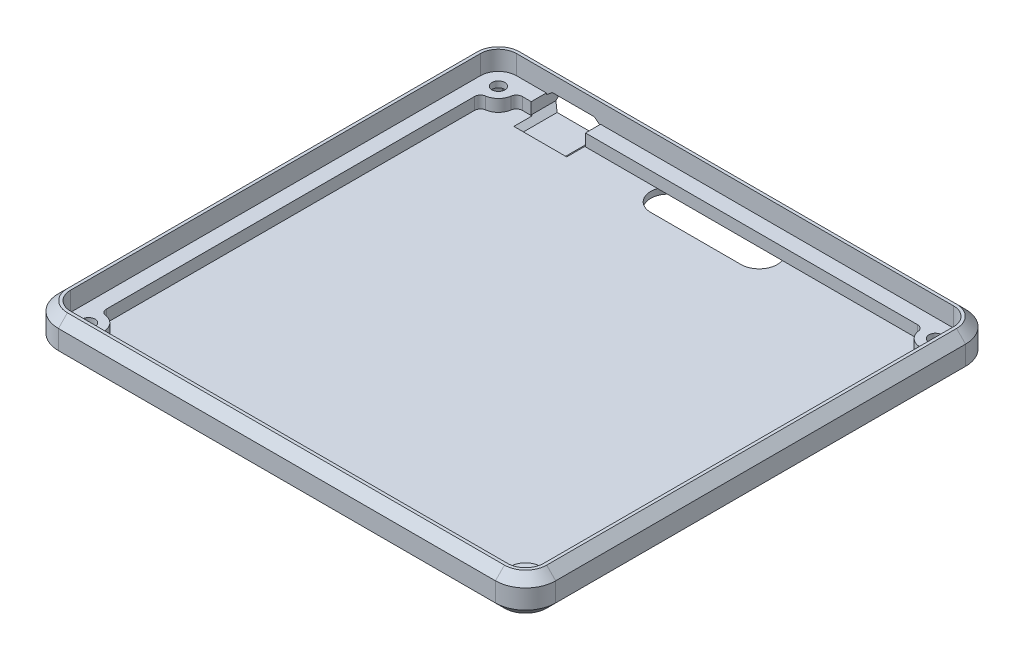
SolidWorks part; units mm, degrees
material "ABS"
ref_plane "Front Plane" through (0, 0, 0) normal (0, 0, 1) x (1, 0, 0)
ref_plane "Top Plane" through (0, 0, 0) normal (0, 1, 0) x (1, 0, 0)
ref_plane "Right Plane" through (0, 0, 0) normal (1, 0, 0) x (0, 0, -1)
sketch "Sketch2" plane through (0, 0, 0) normal (0, 1, 0) x (1, 0, 0)
  line L1 (-72.5, 74) -> (72.5, 74)
  line L2 (-78.5, 68) -> (-78.5, -68)
  line L3 (-72.5, -74) -> (72.5, -74)
  line L4 (78.5, 68) -> (78.5, -68)
  line L5 (-78.5, 74) -> (78.5, -74) construction
  line L6 (-78.5, -74) -> (78.5, 74) construction
  arc A0 (-78.5, -68) -> (-72.5, -74) centre (-72.5, -68) ccw
  arc A1 (-72.5, 74) -> (-78.5, 68) centre (-72.5, 68) ccw
  arc A2 (72.5, 74) -> (78.5, 68) centre (72.5, 68) cw
  arc A3 (72.5, -74) -> (78.5, -68) centre (72.5, -68) ccw
  point P0 (0, 0)
  dimension "D3" = 6
  dimension "D1" = 157
  dimension "D2" = 148
extrude "Boss-Extrude2" add sketch "Sketch2" along normal blind 2
sketch "Sketch3" plane through (0, 2, 0) normal (0, 1, 0) x (1, 0, 0)
  line L0 (-72.5, -74) -> (72.5, -74) construction
  line L1 (78.5, -68) -> (78.5, 68) construction
  line L2 (72.5, 74) -> (-72.5, 74) construction
  line L3 (-78.5, 68) -> (-78.5, -68) construction
  line L4 (-72.5, -74) -> (72.5, -74)
  line L5 (78.5, -68) -> (78.5, 68)
  line L6 (72.5, 74) -> (-72.5, 74)
  line L7 (-78.5, 68) -> (-78.5, -68)
  line L8 (0, -80.5945) -> (0, 82.9206) construction
  line L9 (9.041, 0) -> (-113.0904, 0) construction
  line L10 (-82.5, 68) -> (-82.5, -68)
  line L11 (-72.5, -78) -> (72.5, -78)
  line L12 (82.5, -68) -> (82.5, 68)
  line L13 (72.5, 78) -> (-72.5, 78)
  line L14 (-73.5, 63) -> (-73.5, -63)
  line L15 (-67.5, -69) -> (67.5, -69)
  line L16 (73.5, -63) -> (73.5, 63)
  line L17 (67.5, 69) -> (-67.5, 69)
  line L18 (-73.5, 63) -> (-72.5, 63)
  line L19 (-67.5, 69) -> (-67.5, 68)
  line L20 (-73.5, 68) -> (-73.5, -68) construction
  line L21 (72.5, 69) -> (-72.5, 69) construction
  line L22 (67.5, 69) -> (67.5, 68)
  line L23 (73.5, 63) -> (72.5, 63)
  line L24 (67.5, -69) -> (67.5, -68)
  line L25 (73.5, -63) -> (72.5, -63)
  line L26 (-67.5, -69) -> (-67.5, -68)
  line L27 (-73.5, -63) -> (-72.5, -63)
  line L28 (-72.5, -69) -> (72.5, -69) construction
  line L29 (73.5, -68) -> (73.5, 68) construction
  arc A0 (-78.5, -68) -> (-72.5, -74) centre (-72.5, -68) ccw construction
  arc A1 (72.5, -74) -> (78.5, -68) centre (72.5, -68) ccw construction
  arc A2 (78.5, 68) -> (72.5, 74) centre (72.5, 68) ccw construction
  arc A3 (-72.5, 74) -> (-78.5, 68) centre (-72.5, 68) ccw construction
  arc A4 (-78.5, -68) -> (-72.5, -74) centre (-72.5, -68) ccw
  arc A5 (72.5, -74) -> (78.5, -68) centre (72.5, -68) ccw
  arc A6 (78.5, 68) -> (72.5, 74) centre (72.5, 68) ccw
  arc A7 (-72.5, 74) -> (-78.5, 68) centre (-72.5, 68) ccw
  circle A9 centre (-72.5, -68) radius 2.15
  circle A10 centre (72.5, -68) radius 2.15
  circle A11 centre (72.5, 68) radius 2.15
  circle A12 centre (-72.5, 68) radius 2.15
  arc A13 (-82.5, -68) -> (-72.5, -78) centre (-72.5, -68) ccw
  arc A14 (72.5, -78) -> (82.5, -68) centre (72.5, -68) ccw
  arc A15 (82.5, 68) -> (72.5, 78) centre (72.5, 68) ccw
  arc A16 (-72.5, 78) -> (-82.5, 68) centre (-72.5, 68) ccw
  arc A21 (-72.5, 63) -> (-67.5, 68) centre (-72.5, 68) ccw
  arc A22 (72.5, 63) -> (67.5, 68) centre (72.5, 68) cw
  arc A23 (-72.5, 69) -> (-73.5, 68) centre (-72.5, 68) ccw construction
  arc A24 (72.5, -63) -> (67.5, -68) centre (72.5, -68) ccw
  arc A25 (-72.5, -63) -> (-67.5, -68) centre (-72.5, -68) cw
  arc A26 (-73.5, -68) -> (-72.5, -69) centre (-72.5, -68) ccw construction
  arc A27 (72.5, -69) -> (73.5, -68) centre (72.5, -68) ccw construction
  arc A28 (73.5, 68) -> (72.5, 69) centre (72.5, 68) ccw construction
  arc M10 (-78.5, -68) -> (-72.5, -74) centre (-72.5, -68) ccw
  line M11 (-72.5, -74) -> (72.5, -74)
  arc M12 (72.5, -74) -> (78.5, -68) centre (72.5, -68) ccw
  line M13 (78.5, -68) -> (78.5, 68)
  arc M14 (78.5, 68) -> (72.5, 74) centre (72.5, 68) ccw
  line M15 (72.5, 74) -> (-72.5, 74)
  arc M16 (-72.5, 74) -> (-78.5, 68) centre (-72.5, 68) ccw
  line M17 (-78.5, 68) -> (-78.5, -68)
  dimension "D1" = 68
  dimension "D2" = 4.3
  dimension "D3" = 72.5
  dimension "D4" = 4
  dimension "D6" = 1
  dimension "D7" = 5
  dimension "D8" = 1
  dimension "D9" = 5
  dimension "D5" = 5
extrude "Boss-Extrude3" add sketch "Sketch3" along normal blind 4 and the other way blind 2 contours L13 A16 L10 A13 L11 A14 L12 A15 M10 M17 M16 M15 M14 M13 M12 M11 | L17 L16 L15 L14 M17 M10 M11 M12 M13 M14 M15 M16 region at (-75.217, 2, 70.717) region at (-77.9654, 2, -73.4654)
sketch "Sketch8" plane through (0, 6, 0) normal (0, 1, 0) x (1, 0, 0)
  line L0 (-72.5, -78) -> (72.5, -78) construction
  line L1 (82.5, -68) -> (82.5, 68) construction
  line L2 (72.5, 78) -> (-72.5, 78) construction
  line L3 (-82.5, 68) -> (-82.5, -68) construction
  line L4 (78.5, -68) -> (78.5, 68)
  line L5 (72.5, 74) -> (-72.5, 74)
  line L6 (-78.5, 68) -> (-78.5, -68)
  line L7 (-72.5, -74) -> (72.5, -74)
  line L8 (78.5, -68) -> (78.5, 68)
  line L9 (72.5, 74) -> (-72.5, 74)
  line L10 (-78.5, 68) -> (-78.5, -68)
  line L11 (-72.5, -74) -> (72.5, -74)
  line L12 (-72.5, -78) -> (72.5, -78)
  line L13 (82.5, -68) -> (82.5, 68)
  line L14 (72.5, 78) -> (-72.5, 78)
  line L15 (-82.5, 68) -> (-82.5, -68)
  line L16 (-77.5, 68) -> (-77.5, -68)
  line L17 (-72.5, -73) -> (72.5, -73)
  line L18 (77.5, -68) -> (77.5, 68)
  line L19 (72.5, 73) -> (-72.5, 73)
  arc A0 (-82.5, -68) -> (-72.5, -78) centre (-72.5, -68) ccw construction
  arc A1 (72.5, -78) -> (82.5, -68) centre (72.5, -68) ccw construction
  arc A2 (82.5, 68) -> (72.5, 78) centre (72.5, 68) ccw construction
  arc A3 (-72.5, 78) -> (-82.5, 68) centre (-72.5, 68) ccw construction
  arc A4 (78.5, 68) -> (72.5, 74) centre (72.5, 68) ccw
  arc A5 (-72.5, 74) -> (-78.5, 68) centre (-72.5, 68) ccw
  arc A6 (-78.5, -68) -> (-72.5, -74) centre (-72.5, -68) ccw
  arc A7 (72.5, -74) -> (78.5, -68) centre (72.5, -68) ccw
  arc A8 (78.5, 68) -> (72.5, 74) centre (72.5, 68) ccw
  arc A9 (-72.5, 74) -> (-78.5, 68) centre (-72.5, 68) ccw
  arc A10 (-78.5, -68) -> (-72.5, -74) centre (-72.5, -68) ccw
  arc A11 (72.5, -74) -> (78.5, -68) centre (72.5, -68) ccw
  arc A12 (-82.5, -68) -> (-72.5, -78) centre (-72.5, -68) ccw
  arc A13 (72.5, -78) -> (82.5, -68) centre (72.5, -68) ccw
  arc A14 (82.5, 68) -> (72.5, 78) centre (72.5, 68) ccw
  arc A15 (-72.5, 78) -> (-82.5, 68) centre (-72.5, 68) ccw
  arc A16 (-77.5, -68) -> (-72.5, -73) centre (-72.5, -68) ccw
  arc A17 (72.5, -73) -> (77.5, -68) centre (72.5, -68) ccw
  arc A18 (77.5, 68) -> (72.5, 73) centre (72.5, 68) ccw
  arc A19 (-72.5, 73) -> (-77.5, 68) centre (-72.5, 68) ccw
  line M17 (72.5, 78) -> (-72.5, 78)
  arc M18 (-72.5, 78) -> (-82.5, 68) centre (-72.5, 68) ccw
  line M19 (-82.5, 68) -> (-82.5, -68)
  arc M20 (-82.5, -68) -> (-72.5, -78) centre (-72.5, -68) ccw
  line M21 (-72.5, -78) -> (72.5, -78)
  arc M22 (72.5, -78) -> (82.5, -68) centre (72.5, -68) ccw
  line M23 (82.5, -68) -> (82.5, 68)
  arc M24 (82.5, 68) -> (72.5, 78) centre (72.5, 68) ccw
  dimension "D1" = 0
  dimension "D2" = 5
extrude "Boss-Extrude4" add sketch "Sketch8" along normal blind 6.38 contours A11 L11 A10 L10 A9 L9 A8 L8 M24 M17 M18 M19 M20 M21 M22 M23 region at (-77.9654, 6, 73.4654)
sketch "Sketch9" plane through (0, 0, -78) normal (0, 0, -1) x (-1, 0, 0)
  line L0 (82.5, 0) -> (82.5, 12.38) construction
  line L7 (60.62, 7.11) -> (46.62, 7.11)
  line L8 (46.62, 7.11) -> (44.62, 5.51)
  line L14 (62.62, 5.51) -> (60.62, 7.11)
  line L15 (54.9775, 3.85) -> (29.0731, 3.85) construction
  line L16 (44.62, 5.51) -> (44.62, 2.19)
  line L17 (62.62, 5.51) -> (62.62, 2.19)
  line L18 (53.62, 7.11) -> (53.62, 5.8424) construction
  line L19 (-72.5, 0) -> (72.5, 0) construction
  line L20 (62.62, 2.19) -> (60.62, 0.59)
  line L21 (60.62, 0.59) -> (46.62, 0.59)
  line L22 (46.62, 0.59) -> (44.62, 2.19)
  point P7 (62.62, 3.85)
  point P20 (44.62, 3.85)
  dimension "D2" = 3.85
  dimension "D1" = 28.88
  dimension "D5" = 3.26
  dimension "D6" = 1.66
  dimension "D7" = 18
  dimension "D8" = 14
extrude "Cut-Extrude1" cut sketch "Sketch9" against normal blind 15
fillet "Fillet1" radius 2 8 edges at (-67.5, 4, -69) (-73.5, 4, -63) (-73.5, 4, 63) (-67.5, 4, 69) (73.5, 4, 63) (67.5, 4, 69) (67.5, 4, -69) (73.5, 4, -63)
sketch "Sketch11" plane through (0, 2, 0) normal (0, 1, 0) x (1, 0, 0)
  circle A0 centre (-72.5, 68) radius 2.15
  circle A1 centre (72.5, 68) radius 2.15
  circle A2 centre (72.5, -68) radius 2.15
  circle A3 centre (-72.5, -68) radius 2.15
  dimension "D1" = 4.3
  dimension "D2" = 4.3
  dimension "D3" = 4.3
  dimension "D4" = 4.3
extrude "Cut-Extrude3" cut sketch "Sketch11" against normal through all both and the other way through all contours A3 | A2 | A1 | A0 region at (-72.5, 2, -68) region at (72.5, 2, -68) region at (72.5, 2, 68) region at (-72.5, 2, 68)
sketch "Sketch10" plane through (0, 0, 0) normal (0, -1, 0) x (1, 0, 0)
  line L0 (0, -78) -> (0, 105.632) construction
  line L1 (72.5, -78) -> (-72.5, -78) construction
  line L2 (-82.5, 0) -> (91.4068, 0) construction
  line L3 (-82.5, -68) -> (-82.5, 68) construction
  line L4 (70.4793, 64.5) -> (68.4585, 68)
  line L5 (-68.4585, 68) -> (-70.4793, 71.5)
  line L6 (-70.4793, 71.5) -> (-74.5207, 71.5)
  line L7 (-74.5207, 71.5) -> (-76.5415, 68)
  line L8 (-76.5415, 68) -> (-74.5207, 64.5)
  line L9 (-74.5207, 64.5) -> (-70.4793, 64.5)
  line L10 (-70.4793, 64.5) -> (-68.4585, 68)
  line L11 (74.5207, 64.5) -> (70.4793, 64.5)
  line L12 (76.5415, 68) -> (74.5207, 64.5)
  line L13 (74.5207, 71.5) -> (76.5415, 68)
  line L14 (70.4793, 71.5) -> (74.5207, 71.5)
  line L15 (68.4585, 68) -> (70.4793, 71.5)
  line L16 (74.5207, -64.5) -> (70.4793, -64.5)
  line L17 (76.5415, -68) -> (74.5207, -64.5)
  line L18 (74.5207, -71.5) -> (76.5415, -68)
  line L19 (70.4793, -71.5) -> (74.5207, -71.5)
  line L20 (68.4585, -68) -> (70.4793, -71.5)
  line L21 (70.4793, -64.5) -> (68.4585, -68)
  line L22 (-70.4793, -64.5) -> (-68.4585, -68)
  line L23 (-74.5207, -64.5) -> (-70.4793, -64.5)
  line L24 (-76.5415, -68) -> (-74.5207, -64.5)
  line L25 (-74.5207, -71.5) -> (-76.5415, -68)
  line L26 (-70.4793, -71.5) -> (-74.5207, -71.5)
  line L27 (-68.4585, -68) -> (-70.4793, -71.5)
  line L28 (-72.5, 68) -> (-62.8389, 68)
  circle A0 centre (-72.5, 68) radius 3.5 construction
  circle A1 centre (-72.5, 68) radius 2.15 construction
  dimension "D3" = 7
extrude "Cut-Extrude2" cut sketch "Sketch10" against normal blind 4 contours L9 L10 L5 L6 L7 L8 | L12 L11 L4 L15 L14 L13 | L22 L27 L26 L25 L24 L23 | L17 L16 L21 L20 L19 L18 region at (-69.5615, 0, 66.3035)
chamfer "Chamfer1" distance 3 angle 45 16 edges at (-79.5711, 12.38, 75.0711) (0, 12.38, 78) (79.5711, 12.38, 75.0711) (82.5, 12.38, 0) (79.5711, 12.38, -75.0711) (0, 12.38, -78) (-82.5, 12.38, 0) (-79.5711, 12.38, -75.0711) (-79.5711, 0, -75.0711) (-82.5, 0, 0) (-79.5711, 0, 75.0711) (0, 0, 78) (79.5711, 0, 75.0711) (82.5, 0, 0) (79.5711, 0, -75.0711) (0, 0, -78)
sketch "Sketch13" plane through (0, 6, 0) normal (0, 1, 0) x (1, 0, 0)
  line L0 (-53.62, 63) -> (-53.62, 80.4308) construction
  line L1 (-46.62, 63) -> (-60.62, 63) construction
  line L2 (-44.62, 69) -> (-62.62, 69)
  line L3 (65.5718, 69) -> (-45.2325, 69) construction
  line L4 (-62.0075, 69) -> (-65.5718, 69) construction
  line L5 (-62.62, 69) -> (-62.62, 74)
  line L6 (-62.0075, 74) -> (-72.5, 74) construction
  line L7 (-62.62, 74) -> (-44.62, 74)
  line L8 (72.5, 74) -> (-72.5, 74) construction
  line L9 (-44.62, 74) -> (-44.62, 69)
  dimension "D1" = 9
  dimension "D2" = 9
extrude "Cut-Extrude5" cut sketch "Sketch13" against normal blind 1
sketch "Sketch14" plane through (0, 0, 0) normal (0, -1, 0) x (1, 0, 0)
  line L0 (0, 15.7154) -> (0, -85.3561) construction
  line L2 (72.5, -78) -> (-44.62, -78) construction
  line L3 (-62, -41) -> (-52, -41)
  line L4 (-67, -46) -> (-67, -56)
  line L5 (-62, -61) -> (-52, -61)
  line L6 (-47, -46) -> (-47, -56)
  line L7 (-67, -41) -> (-47, -61) construction
  line L8 (-67, -61) -> (-47, -41) construction
  line L9 (62, -61) -> (52, -61)
  line L10 (47, -46) -> (47, -56)
  line L11 (62, -41) -> (52, -41)
  line L12 (67, -46) -> (67, -56)
  arc A2 (-67, -56) -> (-62, -61) centre (-62, -56) ccw
  arc A3 (-52, -61) -> (-47, -56) centre (-52, -56) ccw
  arc A4 (-52, -41) -> (-47, -46) centre (-52, -46) cw
  arc A5 (-62, -41) -> (-67, -46) centre (-62, -46) ccw
  arc A6 (52, -61) -> (47, -56) centre (52, -56) cw
  arc A7 (52, -41) -> (47, -46) centre (52, -46) ccw
  arc A8 (67, -56) -> (62, -61) centre (62, -56) cw
  arc A9 (62, -41) -> (67, -46) centre (62, -46) cw
  point P3 (-57, -51)
  dimension "D1" = 20
  dimension "D5" = 5
  dimension "D2" = 20
  dimension "D3" = 57
  dimension "D4" = 27
extrude "Cut-Extrude6" cut sketch "Sketch14" against normal blind 1
sketch "Sketch15" plane through (0, 0, 0) normal (0, -1, 0) x (1, 0, 0)
  line L0 (0, 10.9905) -> (0, -88.4375) construction
  line L1 (-15, -67) -> (15, -67) construction
  line L2 (-15, -61) -> (15, -61)
  line L3 (-15, -73) -> (15, -73)
  line L4 (-72.5, -75) -> (72.5, -75) construction
  arc A0 (-15, -61) -> (-15, -73) centre (-15, -67) ccw
  arc A1 (15, -73) -> (15, -61) centre (15, -67) ccw
  point P5 (0, -67)
  dimension "D1" = 8
  dimension "D2" = 12
  dimension "D3" = 30
extrude "Cut-Extrude7" cut sketch "Sketch15" against normal blind 2
